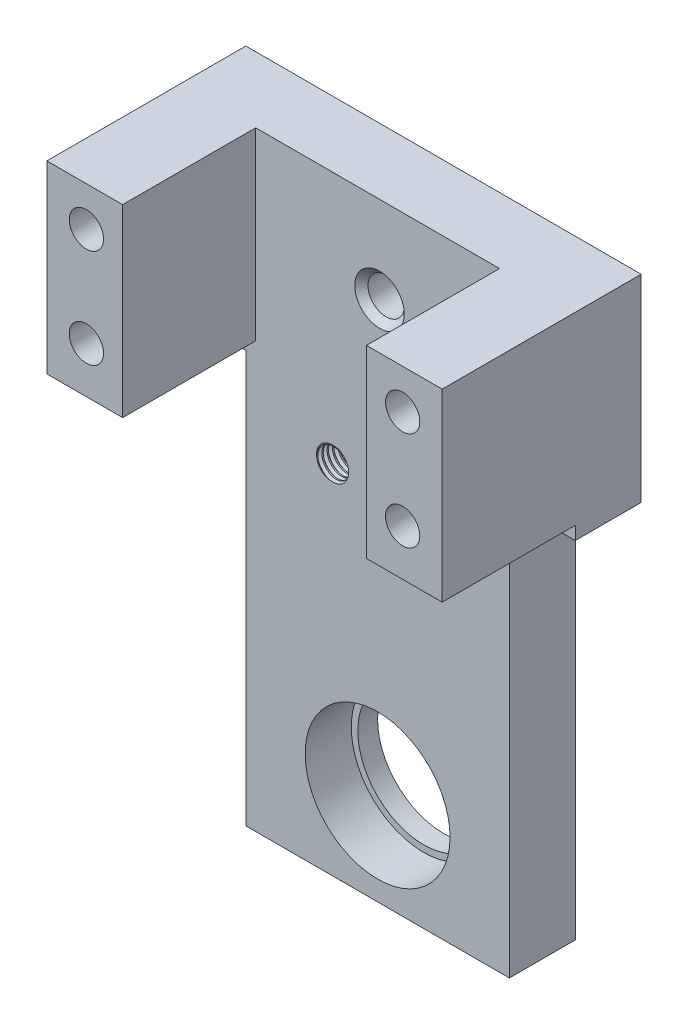
SolidWorks part; units mm, degrees
ref_plane "Ebene vorne" through (0, 0, 0) normal (0, 0, 1) x (1, 0, 0)
ref_plane "Ebene oben" through (0, 0, 0) normal (0, 1, 0) x (1, 0, 0)
ref_plane "Ebene rechts" through (0, 0, 0) normal (1, 0, 0) x (0, 0, -1)
sketch "Skizze1" plane through (0, 0, 0) normal (0, 0, 1) x (1, 0, 0)
  line L1 (0, 0) -> (40, 0)
  line L2 (0, 0) -> (0, 110)
  line L3 (0, 110) -> (40, 110)
  line L4 (40, 0) -> (40, 110)
  dimension "D1" = 40
  dimension "D2" = 110
extrude "Aufsatz-Linear austragen1" add sketch "Skizze1" along normal blind 10
sketch "Skizze2" plane through (0, 0, 0) normal (0, 0, -1) x (-1, 0, 0)
  line L0 (-40, 0) -> (-40, 110) construction
  line L1 (-40, 10) -> (0, 10)
  line L2 (-40, 10) -> (-40, 10.01)
  line L3 (-40, 10.01) -> (0, 10.01)
  line L4 (0, 10) -> (0, 10.01)
  line L5 (0, 110) -> (0, 0) construction
  line L6 (0, 0) -> (-40, 0) construction
  dimension "D1" = 10
  dimension "D2" = 0.01
extrude "Schnitt-Linear austragen1" cut sketch "Skizze2" against normal blind 0.1
sketch "Skizze3" plane through (0, 0, 0.1) normal (0, 0, -1) x (-1, 0, 0)
  line L0 (-40, 10.01) -> (-40, 10) construction
  line L1 (-40, 10) -> (0, 10) construction
  circle A0 centre (-20, 31.5) radius 10
  dimension "D3" = 20
  dimension "D1" = 20
  dimension "D2" = 21.5
extrude "Schnitt-Linear austragen2" cut sketch "Skizze3" against normal blind 11 and the other way blind 7
sketch "Skizze4" plane through (0, 0, 0) normal (0, 0, -1) x (-1, 0, 0)
  circle A0 centre (-20.2905, 96.8) radius 11
  circle A1 centre (-20, 31.5) radius 10 construction
  dimension "D1" = 22
  dimension "D2" = 65.3
sketch "Skizze8" plane through (0, 110, 0) normal (0, 1, 0) x (1, 0, 0)
  line L0 (40, -10) -> (0, -10) construction
  line L1 (-10, 0) -> (50, 0)
  line L2 (-10, 0) -> (-10, -10)
  line L3 (-10, -10) -> (50, -10)
  line L4 (50, 0) -> (50, -10)
  line L5 (31.2905, 0) -> (9.2905, 0) construction
  line L6 (40, -10) -> (40, 0) construction
  line L7 (0, -10) -> (0, 0) construction
  dimension "D1" = 0
  dimension "D2" = 0
  dimension "D3" = 10
  dimension "D4" = 10
extrude "Aufsatz-Linear austragen2" add sketch "Skizze8" against normal blind 30
sketch "Skizze5" plane through (0, 0, 10) normal (0, 0, 1) x (1, 0, 0)
  circle A0 centre (20.2905, 96.8) radius 2.7575
  dimension "D1" = 5.515
extrude "Schnitt-Linear austragen4" cut sketch "Skizze5" against normal blind 7.5
sketch "Skizze6" plane through (0, 0, 2.5) normal (0, 0, 1) x (1, 0, 0)
  circle A0 centre (20.2905, 96.8) radius 11.35
  dimension "D1" = 22.7
extrude "Schnitt-Linear austragen5" cut sketch "Skizze6" against normal blind 2.5
chamfer "Fase1" distance 1 angle 45 2 edges at (10, 31.5, 10) (23.048, 96.8, 10)
sketch "Skizze7" plane through (0, 0, 10) normal (0, 0, 1) x (1, 0, 0)
  circle A0 centre (20, 31.5) radius 11
  dimension "D1" = 22
extrude "Schnitt-Linear austragen7" cut sketch "Skizze7" against normal blind 7
sketch "Skizze9" plane through (0, 0, 10) normal (0, 0, 1) x (1, 0, 0)
  line L0 (50, 80) -> (50, 110) construction
  line L1 (50, 82) -> (38.5, 82)
  line L2 (50, 82) -> (50, 110)
  line L3 (50, 110) -> (38.5, 110)
  line L4 (38.5, 82) -> (38.5, 110)
  line L5 (-10, 80) -> (-10, 110) construction
  line L6 (-10, 110) -> (1.5, 110)
  line L7 (-10, 110) -> (-10, 82)
  line L8 (-10, 82) -> (1.5, 82)
  line L9 (1.5, 110) -> (1.5, 82)
  line L11 (40, 80) -> (50, 80) construction
  line L12 (-10, 80) -> (0, 80) construction
  line L15 (50, 110) -> (-10, 110) construction
  dimension "D1" = 11.5
  dimension "D2" = 11.5
  dimension "D3" = 2
  dimension "D4" = 2
  dimension "D5" = 0
  dimension "D6" = 0
extrude "Aufsatz-Linear austragen3" add sketch "Skizze9" along normal blind 20.2
sketch "Skizze10" plane through (0, 0, 0) normal (0, -1, 0) x (1, 0, 0)
  line L1 (0, 10) -> (40, 10)
  line L2 (0, 10) -> (0, 0)
  line L3 (0, 0) -> (40, 0)
  line L4 (40, 10) -> (40, 0)
extrude "Schnitt-Linear austragen8" cut sketch "Skizze10" against normal blind 17.5
sketch "Skizze11" plane through (0, 0, 0) normal (0, 0, -1) x (-1, 0, 0)
  line L0 (-50, 110) -> (10, 110) construction
  line L1 (-50, 80) -> (-50, 110) construction
  line L3 (10, 80) -> (10, 110) construction
  circle A0 centre (-44, 104) radius 4.5
  circle A1 centre (-44, 89) radius 4.5
  circle A2 centre (4, 104) radius 4.5
  circle A3 centre (4, 89) radius 4.5
  dimension "D9" = 9
  dimension "D10" = 9
  dimension "D11" = 9
  dimension "D12" = 9
  dimension "D1" = 6
  dimension "D2" = 6
  dimension "D3" = 6
  dimension "D4" = 21
  dimension "D5" = 6
  dimension "D6" = 21
  dimension "D7" = 6
  dimension "D8" = 6
extrude "Schnitt-Linear austragen9" cut sketch "Skizze11" against normal blind 19
sketch "Skizze12" plane through (0, 0, 19) normal (0, 0, -1) x (-1, 0, 0)
  circle A0 centre (-44, 104) radius 2.6
  circle A2 centre (4, 104) radius 2.6
  circle A3 centre (4, 89) radius 2.6
  circle A4 centre (-44, 89) radius 2.6
  dimension "D1" = 5.2
extrude "Schnitt-Linear austragen10" cut sketch "Skizze12" against normal blind 17.5
sketch "Skizze13" plane through (0, 0, 0) normal (0, 0, -1) x (-1, 0, 0)
  line L0 (-40, 17.5) -> (-40, 80) construction
  line L5 (0, 80) -> (0, 17.5) construction
  circle A0 centre (-27, 71.55) radius 2.25
  circle A1 centre (-13, 71.55) radius 2.25
  dimension "D1" = 4.5
  dimension "D2" = 4.5
  dimension "D3" = 25.25
  dimension "D4" = 25.25
  dimension "D5" = 13
  dimension "D6" = 13
extrude "Schnitt-Linear austragen11" cut sketch "Skizze13" against normal blind 18
thread "Gewinde1" pitch 0.8 method cut profile "Gewindeprofil1" start angle 0, offset 0, length 10, pitch 0.8, diameter 4.5
ref_plane "Ebene1" through (29.25, 71.55, 0) normal (0, -1, 0) x (1, 0, 0)
sketch "Gewindeprofil1" plane through (29.25, 71.55, 0) normal (0, -1, 0) x (1, 0, 0)
  line L0 (0, 0) -> (0, 0.8) construction
  line L1 (0, 0) -> (0.433, 0.25)
  line L2 (0.433, 0.25) -> (0.433, 0.35)
  line L3 (0.433, 0.35) -> (0, 0.6)
  line L4 (0.433, 0.3) -> (0, 0.3) construction
  line L11 (0, 0) -> (0, 0.6)
  point P2 (0, 0)
  dimension "Pitch" = 0.8
  dimension "Profile_Angle" = 60
  dimension "Profile_Land" = 0.1
  dimension "Profile_Height" = 0.433
thread "Gewinde2" pitch 0.8 method cut profile "Gewindeprofil2" start angle 0, offset 0, length 10, pitch 0.8, diameter 4.5
ref_plane "Ebene2" through (15.25, 71.55, 0) normal (0, -1, 0) x (1, 0, 0)
sketch "Gewindeprofil2" plane through (15.25, 71.55, 0) normal (0, -1, 0) x (1, 0, 0)
  line L0 (0, 0) -> (0, 0.8) construction
  line L1 (0, 0) -> (0.433, 0.25)
  line L2 (0.433, 0.25) -> (0.433, 0.35)
  line L3 (0.433, 0.35) -> (0, 0.6)
  line L4 (0.433, 0.3) -> (0, 0.3) construction
  line L11 (0, 0) -> (0, 0.6)
  point P2 (0, 0)
  dimension "Pitch" = 0.8
  dimension "Profile_Angle" = 60
  dimension "Profile_Land" = 0.1
  dimension "Profile_Height" = 0.433
